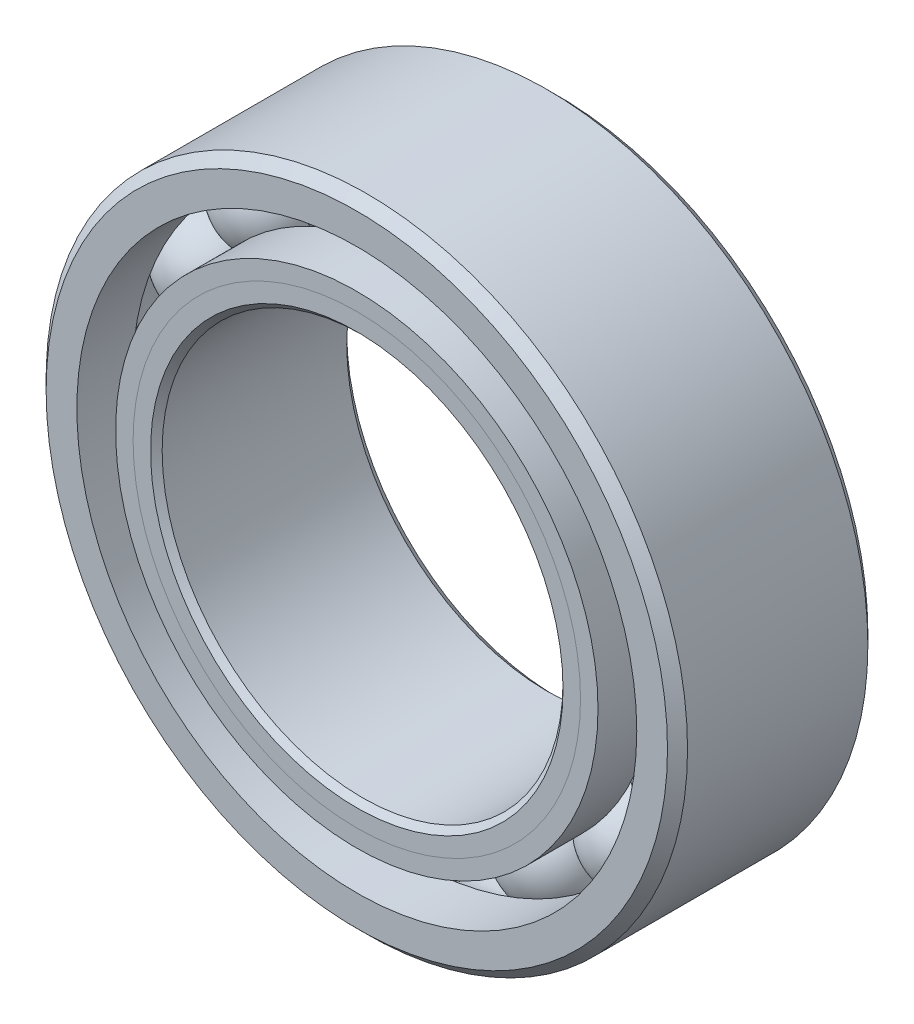
SolidWorks part; units mm, degrees
ref_plane "Front Plane" through (0, 0, 0) normal (0, 0, 1) x (1, 0, 0)
ref_plane "Top Plane" through (0, 0, 0) normal (0, 1, 0) x (1, 0, 0)
ref_plane "Right Plane" through (0, 0, 0) normal (1, 0, 0) x (0, 0, -1)
sketch "Sketch1" plane through (0, 0, 0) normal (1, 0, 0) x (0, 0, -1)
  line L0 (-1.9837, 0) -> (1.9837, 0) construction
  line L1 (0, 6.35) -> (0, -6.35) construction
  line L2 (1.7854, 6.35) -> (-1.7854, 6.35)
  line L3 (-1.7854, 6.35) -> (-1.9837, 6.1516)
  line L4 (-1.9837, 6.1516) -> (-1.9837, 5.5432)
  line L5 (-1.9837, 5.5432) -> (-0.8817, 5.5432)
  line L6 (1.9837, 5.5432) -> (0.8817, 5.5432)
  line L7 (1.9837, 6.1516) -> (1.9837, 5.5432)
  line L8 (1.7854, 6.35) -> (1.9837, 6.1516)
  line L9 (0, 6.35) -> (0, 5.1594) construction
  line L10 (0, 5.1594) -> (0, 3.9688) construction
  arc A0 (-0.8817, 5.5432) -> (0.8817, 5.5432) centre (0, 5.1594) cw
  point P14 (0, 3.9688)
  dimension "D3" = 1.7633
  dimension "D1" = 45
  dimension "Width" = 3.9675
  dimension "OD" = 12.7
  dimension "D2" = 0.1984
  dimension "Shaft Dia" = 7.9375
  dimension "D4" = 0.3838
revolve "Revolve1" add sketch "Sketch1" angle 360 about L0
sketch "Sketch2" plane through (0, 0, 0) normal (1, 0, 0) x (0, 0, -1)
  line L0 (-1.9837, 4.7755) -> (-0.8817, 4.7755)
  line L1 (-1.9837, 6.1516) -> (-1.9837, -6.1516) construction
  line L2 (-1.9837, 4.7755) -> (-1.9837, 4.4294)
  line L3 (-1.9837, 4.4294) -> (-1.6376, 4.0833)
  line L4 (-1.6376, 4.0833) -> (0, 4.0833)
  line L5 (0, 6.35) -> (0, -6.35) construction
  line L6 (0, 4.0833) -> (0, 4.1978)
  line L7 (0, 4.1978) -> (0, 3.9688) construction
  line L8 (-1.9837, 4.7755) -> (-1.9837, 4.0833) construction
  line L9 (-1.9837, 4.0833) -> (-1.6376, 4.0833) construction
  arc A0 (-0.8817, 4.7755) -> (0, 4.1978) centre (0, 5.1594) ccw
  arc A1 (0.8817, 5.5432) -> (-0.8817, 5.5432) centre (0, 5.1594) ccw construction
  circle A2 centre (0, 5.1594) radius 0.9616 construction
  dimension "D1" = 45
revolve "Revolve2" add sketch "Sketch2" angle 360 about L0
sketch "Sketch3" plane through (0, 0, 0) normal (1, 0, 0) x (0, 0, -1)
  line L0 (-1.9837, 4.4294) -> (-1.6376, 4.0833)
  line L1 (-1.6376, 4.0833) -> (0, 4.0833)
  line L2 (0, 4.0833) -> (0, 4.1978)
  line L3 (-1.9837, 4.4294) -> (-1.9837, 4.0833)
  line L4 (-1.9837, 4.7755) -> (-1.9837, 4.0833) construction
  line L5 (-1.9837, 4.0833) -> (-1.8692, 3.9688)
  line L6 (-1.8692, 3.9688) -> (1.7854, 3.9688)
  line L7 (1.7854, 6.35) -> (1.7854, -6.35) construction
  line L8 (1.7854, 3.9688) -> (1.9837, 4.1671)
  line L9 (1.9837, -6.1516) -> (1.9837, 6.1516) construction
  line L10 (1.9837, 4.1671) -> (1.9837, 4.7755)
  line L11 (1.9837, 4.7755) -> (0.8817, 4.7755)
  line L13 (1.7854, 6.35) -> (1.9837, 6.1516) construction
  circle A0 centre (0, 5.1594) radius 0.9616 construction
  arc A1 (0.8817, 4.7755) -> (0, 4.1978) centre (0, 5.1594) cw
revolve "Revolve3" add sketch "Sketch3" angle 360 about L0
sketch "Sketch4" plane through (0, 0, 0) normal (1, 0, 0) x (0, 0, -1)
  line L0 (-0.9616, 5.1594) -> (0.9616, 5.1594)
  circle A1 centre (0, 5.1594) radius 0.9616 construction
  arc A2 (-0.9616, 5.1594) -> (0.9616, 5.1594) centre (0, 5.1594) cw
  arc A3 (0.8817, 5.5432) -> (-0.8817, 5.5432) centre (0, 5.1594) ccw construction
revolve "Revolve4" add sketch "Sketch4" angle 360 about L0
ref_axis "Axis1" through (0, 0, -1.9837) along (0, 0, 1)
pattern_circular "CirPattern1" count 16 every 22.5 about axis through (0, 0, -1.9837) along (0, 0, 1) of bodies 104
equation "\"D2@Sketch1\" = \"Width@Sketch1\"*.05"
equation "\"D3@Sketch1\" = \"Width@Sketch1\"/2.25"
equation "\"D4@Sketch1\" = (((\"OD@Sketch1\"-\"Width@Sketch1\")/2)/3.25)/3.5"
equation "\"D2@CirPattern1\" = 360/\"Balls@CirPattern1\""
